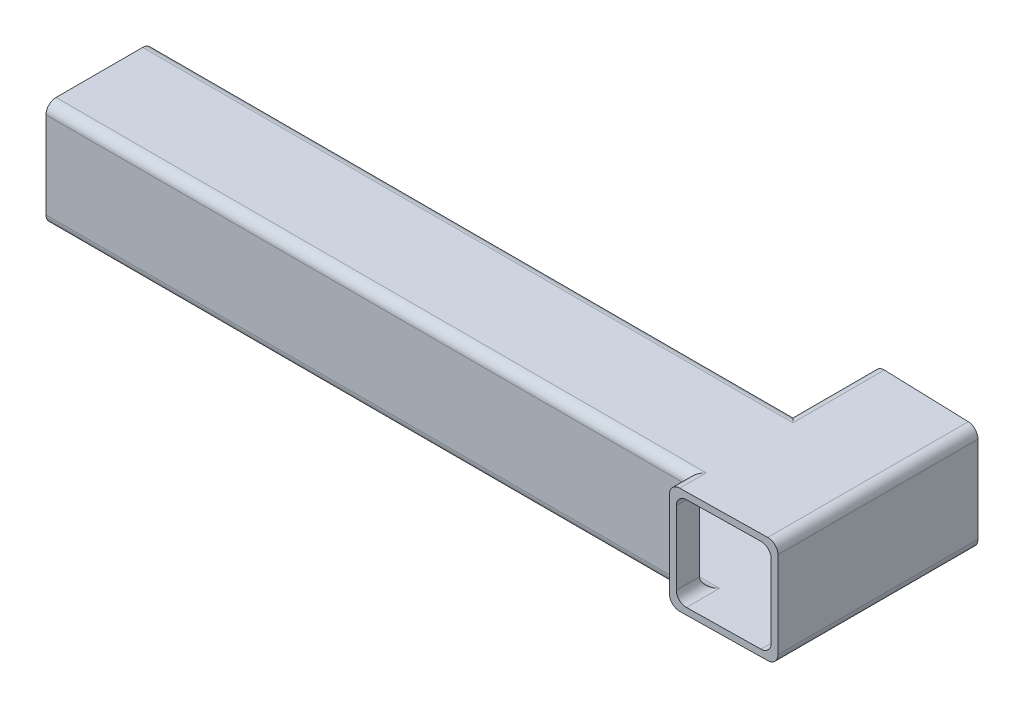
SolidWorks part; units mm, degrees
ref_plane "Front Plane" through (0, 0, 0) normal (0, 0, 1) x (1, 0, 0)
ref_plane "Top Plane" through (0, 0, 0) normal (0, 1, 0) x (1, 0, 0)
ref_plane "Right Plane" through (0, 0, 0) normal (1, 0, 0) x (0, 0, -1)
sketch "Sketch1" plane through (0, 0, 0) normal (1, 0, 0) x (0, 0, -1)
  line L0 (3.175, 22.225) -> (47.625, 22.225)
  line L1 (0, -25.4) -> (50.8, -25.4)
  line L2 (0, -25.4) -> (0, 25.4)
  line L3 (0, 25.4) -> (50.8, 25.4)
  line L4 (50.8, -25.4) -> (50.8, 25.4)
  line L5 (0, -25.4) -> (50.8, 25.4) construction
  line L6 (0, 25.4) -> (50.8, -25.4) construction
  line L7 (47.625, -22.225) -> (47.625, 22.225)
  line L8 (3.175, -22.225) -> (47.625, -22.225)
  line L9 (3.175, -22.225) -> (3.175, 22.225)
  line L10 (0, -31.4743) -> (0, 34.7184) construction
  line L11 (-8.1938, 0) -> (66.3216, 0) construction
  point P0 (25.4, 0)
  dimension "D1" = 50.8
  dimension "D2" = 50.8
  dimension "D3" = 3.175
extrude "Boss-Extrude1" add sketch "Sketch1" along normal blind 304.8 contours L1 L4 L3 L2 L8 L9 L0 L7 region at (0, 0, -0.7184)
sketch "Sketch2" plane through (0, 0, 0) normal (0, 0, 1) x (1, 0, 0)
  line L0 (-9.0901, 0) -> (390.0692, 0) construction
  line L1 (307.9623, 22.225) -> (352.4377, 22.225)
  line L2 (304.7873, -25.4) -> (355.6127, -25.4)
  line L3 (304.7873, -25.4) -> (304.7873, 25.4)
  line L4 (304.7873, 25.4) -> (355.6127, 25.4)
  line L5 (355.6127, -25.4) -> (355.6127, 25.4)
  line L6 (304.7873, -25.4) -> (355.6127, 25.4) construction
  line L7 (304.7873, 25.4) -> (355.6127, -25.4) construction
  line L8 (352.4377, -22.225) -> (352.4377, 22.225)
  line L9 (307.9623, -22.225) -> (352.4377, -22.225)
  line L10 (307.9623, -22.225) -> (307.9623, 22.225)
  point P4 (330.2, 0)
  dimension "D1" = 50.8254
  dimension "D2" = 330.2
  dimension "D3" = 50.8
  dimension "D4" = 3.175
extrude "Boss-Extrude2" add sketch "Sketch2" along normal blind 7.9375 and the other way blind 89.6938 contours L2 L5 L4 L3 L9 L10 L1 L8 region at (305.5059, 0, 0)
sketch "Sketch3" plane through (0, 25.4, 0) normal (0, 1, 0) x (1, 0, 0)
  line L0 (304.7873, 89.6938) -> (355.6127, 88.1063)
  line L1 (304.7873, 89.6938) -> (355.6127, 89.6938) construction
  line L2 (355.6127, 89.6938) -> (355.6127, -7.9375) construction
  line L3 (355.6127, 88.1063) -> (355.6127, 89.6938)
  line L4 (355.6127, 89.6938) -> (304.7873, 89.6938)
  line L5 (304.7873, -7.9375) -> (355.6127, -7.1437)
  line L6 (355.6127, -7.1437) -> (355.6127, -7.9375)
  line L7 (355.6127, -7.9375) -> (304.7873, -7.9375)
  dimension "D1" = 0.7937
  dimension "D2" = 95.25
extrude "Cut-Extrude1" cut sketch "Sketch3" against normal through all
fillet "Fillet1" radius 4.7625 10 edges at (152.3936, -25.4, 0) (152.3936, -25.4, -50.8) (152.3936, 25.4, -50.8) (152.3936, 25.4, 0) (304.7873, 25.4, -70.2469) (355.6127, 25.4, -40.4812) (355.6127, -25.4, -40.4812) (304.7873, -25.4, -70.2469) (304.7873, 25.4, 3.9688) (304.7873, -25.4, 3.9688)
ref_plane "Plane1" through (0, -22.225, -47.625) normal (0, 1, 0) x (1, 0, 0)
extrude "Cut-Extrude2" cut sketch "Sketch1<3>" along normal up to next contours L9 L8 L7 L0 region at (0, 0, -25.4)
sketch "Sketch1<3>" plane through (0, 0, 0) normal (1, 0, 0) x (0, 0, -1) same geometry as "Sketch1"
fillet "Fillet3" radius 4.7625 10 edges at (352.4377, -22.225, -40.506) (352.4377, 22.225, -40.506) (307.9623, 22.225, -68.6098) (307.9623, 22.225, 2.3565) (307.9623, -22.225, 2.3565) (307.9623, -22.225, -68.6098) (153.9811, -22.225, -3.175) (153.9811, -22.225, -47.625) (153.9811, 22.225, -47.625) (153.9811, 22.225, -3.175)
